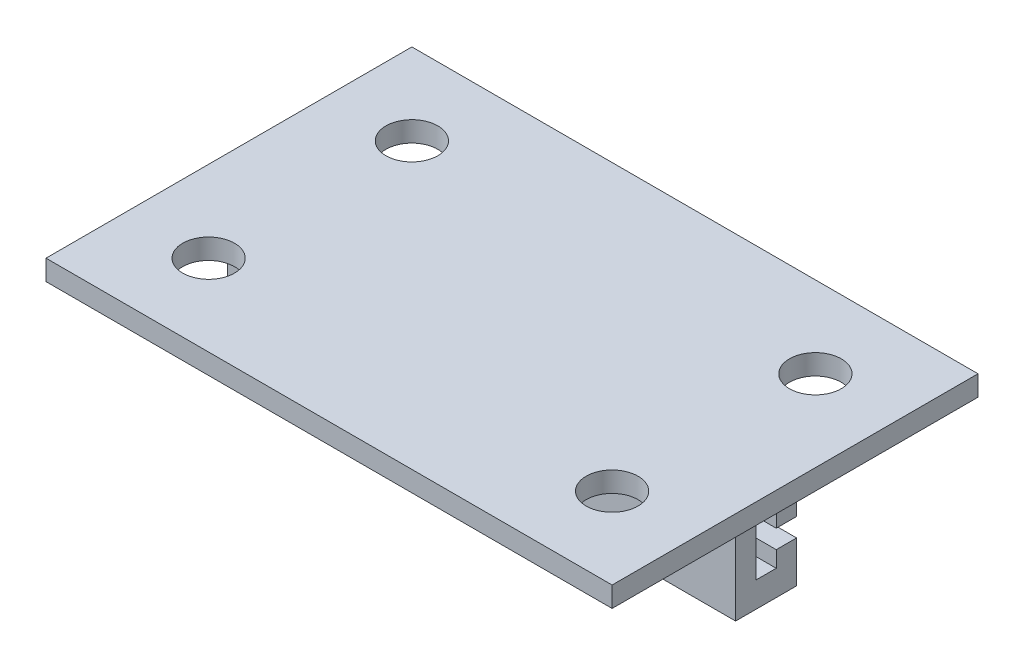
SolidWorks part; units mm, degrees
ref_plane "Front Plane" through (0, 0, 0) normal (0, 0, 1) x (1, 0, 0)
ref_plane "Top Plane" through (0, 0, 0) normal (0, 1, 0) x (1, 0, 0)
ref_plane "Right Plane" through (0, 0, 0) normal (1, 0, 0) x (0, 0, -1)
sketch "Sketch1" plane through (0, 0, 0) normal (1, 0, 0) x (0, 0, -1)
  line L0 (0, 0) -> (6.25, 0)
  line L2 (4, 2.5) -> (2, 2.5)
  line L3 (2, 2.5) -> (2, 7.5)
  line L4 (2, 7.5) -> (4, 7.5)
  line L6 (6.25, 10) -> (0, 10)
  line L7 (0, 10) -> (0, 0)
  line L8 (4, 7.5) -> (4, 5.9125)
  line L9 (4, 5.9125) -> (6, 5.9125)
  line L10 (6, 5.9125) -> (6, 10)
  line L11 (6, 10) -> (6.25, 10)
  line L12 (4, 2.5) -> (4, 4.0875)
  line L13 (4, 4.0875) -> (6, 4.0875)
  line L14 (6, 4.0875) -> (6, 0)
  line L15 (6, 0) -> (6.25, 0)
  dimension "D1" = 5
  dimension "D2" = 1.5875
  dimension "D3" = 2
  dimension "D4" = 2
  dimension "D5" = 2
  dimension "D6" = 10
extrude "Boss-Extrude1" add sketch "Sketch1" along normal blind 50 contours L14 L13 L12 L2 L3 L4 L8 L9 L10 L6 L7 L0 region at (0, 5, -0.1166)
sketch "Sketch2" plane through (0, 10, 0) normal (0, 1, 0) x (1, 0, 0)
  line L1 (-2.85, -15) -> (52.85, -15)
  line L2 (-2.85, -15) -> (-2.85, 21)
  line L3 (-2.85, 21) -> (52.85, 21)
  line L4 (52.85, -15) -> (52.85, 21)
  line L5 (0, 3) -> (50, 3) construction
  line L6 (0, 6) -> (0, 0) construction
  line L7 (50, 6) -> (50, 0) construction
  line L8 (-2.85, 3) -> (52.85, 3) construction
  line L9 (25, 21) -> (25, -15) construction
  line L10 (25, 6) -> (25, 0) construction
  line L11 (50, 6) -> (0, 6) construction
  line L12 (50, 0) -> (0, 0) construction
  line L13 (5.15, -7) -> (44.85, -7) construction
  line L14 (5.15, 13) -> (44.85, 13) construction
  circle A0 centre (5.15, 13) radius 2.55
  circle A1 centre (44.85, 13) radius 2.55
  circle A2 centre (44.85, -7) radius 2.55
  circle A3 centre (5.15, -7) radius 2.55
  dimension "D1" = 5.1
  dimension "D2" = 39.7
  dimension "D3" = 20
  dimension "D4" = 39.7
  dimension "D5" = 8
  dimension "D6" = 8
  dimension "D7" = 8
extrude "Boss-Extrude2" add sketch "Sketch2" along normal blind 2
